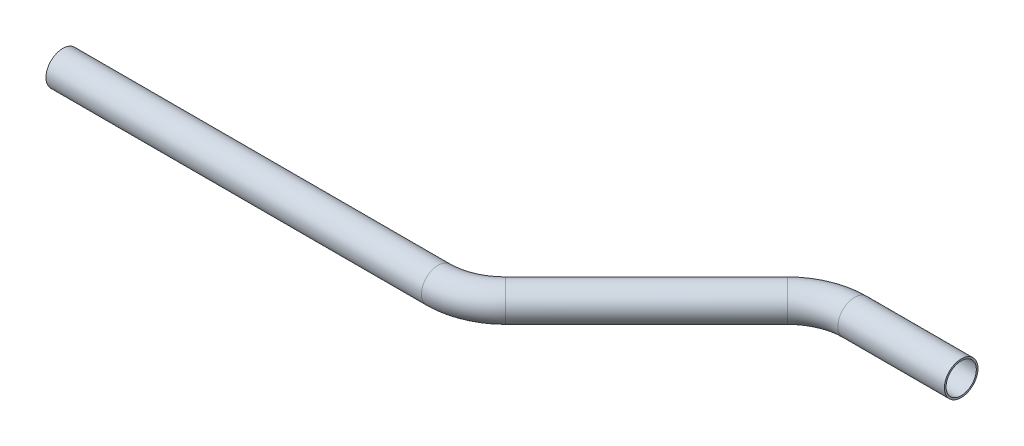
SolidWorks part; units mm, degrees
ref_plane "Front Plane" through (0, 0, 0) normal (0, 0, 1) x (1, 0, 0)
ref_plane "Top Plane" through (0, 0, 0) normal (0, 1, 0) x (1, 0, 0)
ref_plane "Right Plane" through (0, 0, 0) normal (1, 0, 0) x (0, 0, -1)
sketch "Sketch1" plane through (0, 0, 0) normal (0, 1, 0) x (1, 0, 0)
  line L0 (0, 0) -> (141.879, 0)
  line L1 (159.8395, 7.4395) -> (213.1167, 60.7167)
  line L2 (231.0772, 68.1561) -> (271.3561, 68.1561)
  arc A0 (213.1167, 60.7167) -> (231.0772, 68.1561) centre (231.0772, 42.7561) cw
  arc A1 (141.879, 0) -> (159.8395, 7.4395) centre (141.879, 25.4) ccw
  point P7 (220.5561, 68.1561)
  point P10 (152.4, 0)
  dimension "D5" = 25.4
  dimension "D1" = 152.4
  dimension "D2" = 50.8
  dimension "D3" = 135
  dimension "D4" = 68.1561
ref_plane "Plane1" through (0, 0, 0) normal (1, 0, 0) x (0, 0, -1)
sketch "Sketch2" plane through (0, 0, 0) normal (1, 0, 0) x (0, 0, -1)
  circle A0 centre (0, 0) radius 6.35
  circle A1 centre (0, 0) radius 5.715
  dimension "D1" = 12.7
  dimension "D2" = 0.635
sweep "Sweep1" add profiles "Sketch2" path "Sketch1"
